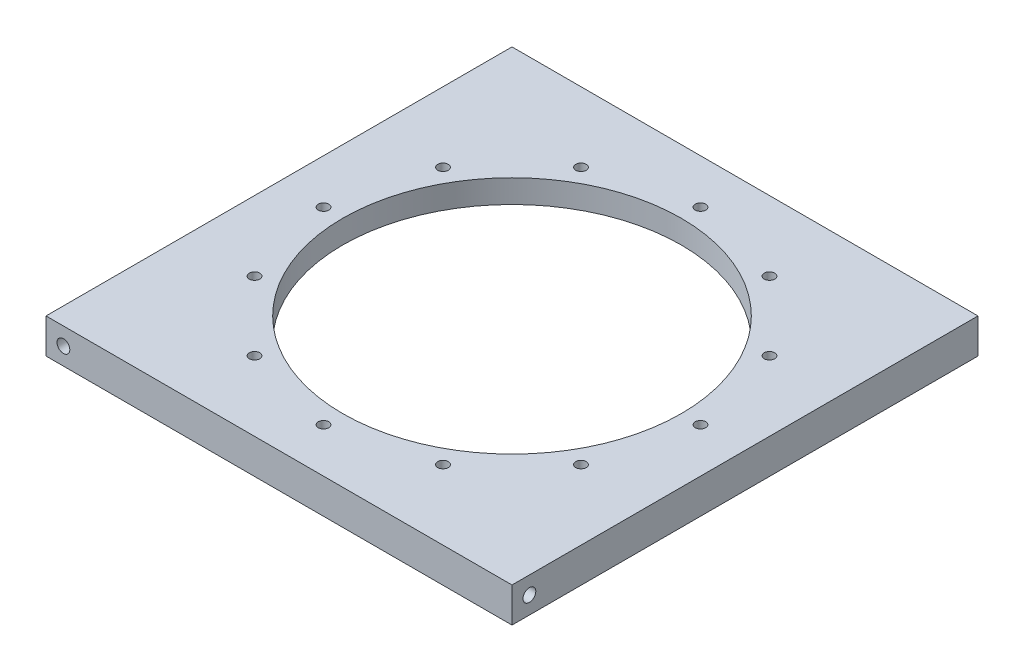
SolidWorks part; units mm, degrees
material "6061-T6 (SS)"
ref_plane "Front Plane" through (0, 0, 0) normal (0, 0, 1) x (1, 0, 0)
ref_plane "Top Plane" through (0, 0, 0) normal (0, 1, 0) x (1, 0, 0)
ref_plane "Right Plane" through (0, 0, 0) normal (1, 0, 0) x (0, 0, -1)
sketch "Sketch1" plane through (0, 0, 0) normal (0, 1, 0) x (1, 0, 0)
  line L5 (0, 0) -> (127.635, 0)
  line L6 (0, 0) -> (0, 127.635)
  line L7 (0, 127.635) -> (127.635, 127.635)
  line L8 (127.635, 0) -> (127.635, 127.635)
  dimension "D1" = 127.635
  dimension "D2" = 127.635
extrude "Boss-Extrude1" add sketch "Sketch1" along normal blind 9.525 contours L5 L8 L7 L6
sketch "Sketch5" plane through (0, 9.525, 0) normal (0, 1, 0) x (1, 0, 0)
  line L0 (63.8175, 0) -> (63.8175, 127.635) construction
  line L3 (0, 0) -> (127.635, 0) construction
  line L8 (0, 127.635) -> (127.635, 127.635) construction
  circle A0 centre (63.8175, 63.8175) radius 46.355
  dimension "D1" = 92.71
extrude "Cut-Extrude1" cut sketch "Sketch5" against normal blind 9.525 contours L0 A0 | A0 L0
sketch "Sketch6" plane through (127.635, 0, 0) normal (1, 0, 0) x (0, 0, -1)
  circle A0 centre (4.7625, 4.7625) radius 1.7526
  dimension "D1" = 3.5052
extrude "6-32 hole1" cut sketch "Sketch6" against normal blind 6.35
sketch "Sketch7" plane through (0, 0, -127.635) normal (0, 0, -1) x (-1, 0, 0)
  circle A0 centre (-122.8725, 4.7625) radius 1.7526
  dimension "D1" = 3.5052
sketch "Sketch8" plane through (0, 0, 0) normal (-1, 0, 0) x (0, 0, 1)
  circle A0 centre (-122.8725, 4.7625) radius 1.7526
  dimension "D1" = 3.5052
sketch "Sketch9" plane through (0, 0, 0) normal (0, 0, 1) x (1, 0, 0)
  circle A0 centre (4.7625, 4.7625) radius 1.7526
  dimension "D1" = 3.5052
extrude "6-32 hole2" cut sketch "Sketch7" against normal blind 6.35
extrude "6-32 hole3" cut sketch "Sketch8" against normal blind 6.35
extrude "6-32 hole4" cut sketch "Sketch9" against normal blind 6.35
sketch "Sketch10" plane through (0, 0, 0) normal (0, -1, 0) x (1, 0, 0)
  circle A0 centre (63.8175, -63.8175) radius 56.3562
  dimension "D1" = 112.7125
extrude "Cut-Extrude2" cut sketch "Sketch10" against normal blind 3.175
sketch "Sketch11" plane through (0, 9.525, 0) normal (0, 1, 0) x (1, 0, 0)
  line L0 (63.8175, 63.8175) -> (63.8175, 115.443) construction
  circle A0 centre (63.8175, 115.443) radius 1.4351
  dimension "D2" = 2.8702
  dimension "D1" = 51.6255
extrude "Cut-Extrude3" cut sketch "Sketch11" against normal through all contours A0
pattern_circular "CirPattern1" count 12 over 360 about axis through (63.8175, 9.525, -63.8175) along (0, 1, 0) of "Cut-Extrude3"
